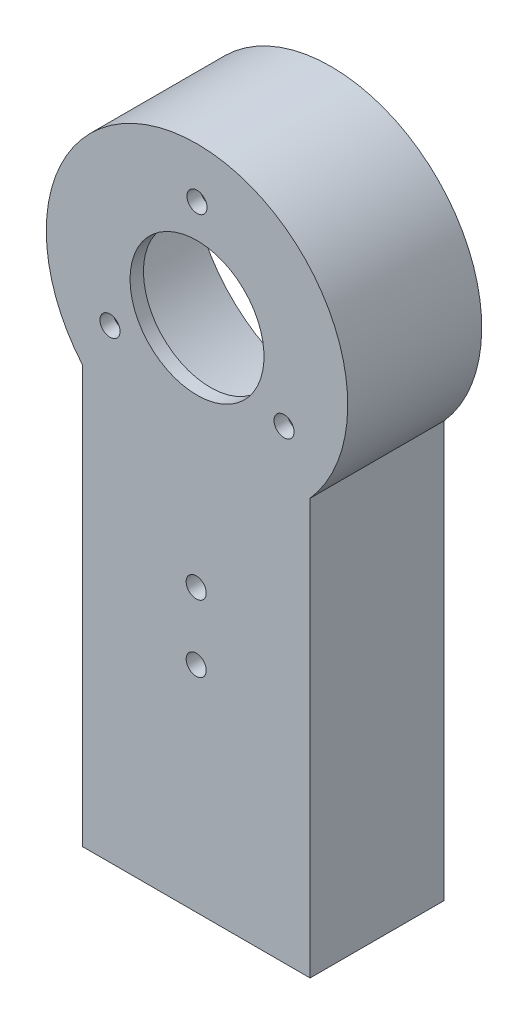
SolidWorks part; units mm, degrees
ref_plane "Front Plane" through (0, 0, 0) normal (0, 0, 1) x (1, 0, 0)
ref_plane "Top Plane" through (0, 0, 0) normal (0, 1, 0) x (1, 0, 0)
ref_plane "Right Plane" through (0, 0, 0) normal (1, 0, 0) x (0, 0, -1)
sketch "Sketch1" plane through (0, 0, 0) normal (0, 0, 1) x (1, 0, 0)
  line L1 (-17.1236, -14.5956) -> (-17.1236, -76.9)
  line L2 (16.8764, -14.8808) -> (16.8764, -76.9)
  line L3 (-17.1236, -76.9) -> (16.8764, -76.9)
  circle A0 centre (0, 0) radius 22.5
  arc A1 (-17.1236, -14.5956) -> (16.8764, -14.8808) centre (0, 0) ccw
  circle A2 centre (-0.1236, -44.9) radius 1.5
  circle A3 centre (-0.1236, -34.9) radius 1.5
  dimension "D1" = 45
  dimension "D4" = 3
  dimension "D5" = 3
  dimension "D6" = 32
  dimension "D7" = 42
  dimension "D2" = 76.9
  dimension "D3" = 34
extrude "Boss-Extrude1" add sketch "Sketch1" along normal blind 20 contours A0 L1 L3 L2 | A0 L1 region at (-0.1354, -48.5303, 0) region at (0, 0, 0)
sketch "Sketch2" plane through (0, 0, 0) normal (0, 0, -1) x (-1, 0, 0)
  circle A0 centre (0, 0) radius 10
  dimension "D1" = 20
extrude "Cut-Extrude1" cut sketch "Sketch2" against normal blind 20
sketch "Sketch3" plane through (0, 0, 0) normal (0, 0, -1) x (-1, 0, 0)
  circle A0 centre (0, 15) radius 1.5
  circle A1 centre (12.9904, -7.5) radius 1.5
  circle A2 centre (-12.9904, -7.5) radius 1.5
  point P10 (0, 0)
  dimension "D1" = 3
  dimension "D2" = 15
  dimension "D3" = 3
extrude "Cut-Extrude2" cut sketch "Sketch3" against normal blind 20
sketch "Sketch4" plane through (0, 0, 0) normal (0, 0, -1) x (-1, 0, 0)
  circle A0 centre (0, 0) radius 21
  dimension "D1" = 42
extrude "Cut-Extrude3" cut sketch "Sketch4" against normal blind 18
